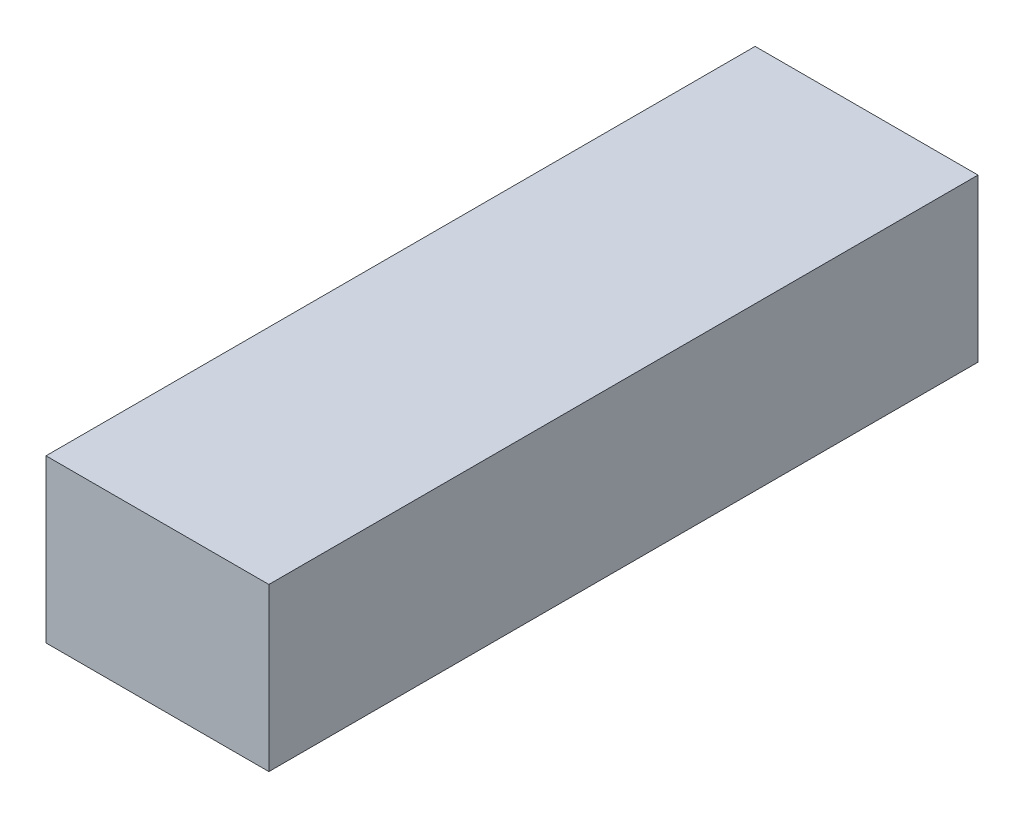
SolidWorks part; units mm, degrees
ref_plane "Front Plane" through (0, 0, 0) normal (0, 0, 1) x (1, 0, 0)
ref_plane "Top Plane" through (0, 0, 0) normal (0, 1, 0) x (1, 0, 0)
ref_plane "Right Plane" through (0, 0, 0) normal (1, 0, 0) x (0, 0, -1)
sketch "Sketch1" plane through (0, 0, 0) normal (0, 1, 0) x (1, 0, 0)
  line L0 (-573.6248, 0) -> (28107.6174, 0) construction
  line L1 (0, -573.6248) -> (0, 28107.6174) construction
  line L3 (-16.5, 52.5) -> (16.5, 52.5)
  line L4 (-16.5, 52.5) -> (-16.5, -52.5)
  line L5 (-16.5, -52.5) -> (16.5, -52.5)
  line L6 (16.5, 52.5) -> (16.5, -52.5)
  line L7 (-16.5, 52.5) -> (16.5, -52.5) construction
  line L8 (-16.5, -52.5) -> (16.5, 52.5) construction
  point P4 (0, 0)
  dimension "D1" = 33
  dimension "D2" = 105
extrude "Boss-Extrude1" add sketch "Sketch1" along normal blind 24
equation "\"Frame_Size\" = 220"
equation "\"Frame_Thickness\" = 6"
equation "\"Arm_Width\" = 30"
equation "\"Motor_Mount_Hole_Diameter\" = 8"
equation "\"Motor_Shaft_Diameter\" = 3"
equation "\"Screw_Nut_Diameter\" = 5"
equation "\"Screw_Diameter\" = 3"
equation "\"Screw_Shaft_Length\" = 10"
equation "\"Screw_Hole_Separation_C2C\" = 20"
equation "\"Solder_Board_Small_Screw_Hole_Separation\" = 37"
equation "\"Solder_Board_Small_Screw_Hole_Diameter\" = 3.3"
equation "\"Solder_Board_Small_Length\" = 45.72"
equation "\"Solder_Board_Small_Width\" = 33.02"
equation "\"Solder_Board_Small_Thickness\" = 1.6"
equation "\"ESC_Length\" = 35"
equation "\"ESC_Width\" = 17"
equation "\"ESC_Thickness\" = 5"
equation "\"Battery_Length\" = 105"
equation "\"Battery_Width\" = 33"
equation "\"Battery_Thickness\" = 24"
equation "\"D1@Sketch1\"=\"Battery_Width\""
equation "\"D1@Boss-Extrude1\"=\"Battery_Thickness\""
